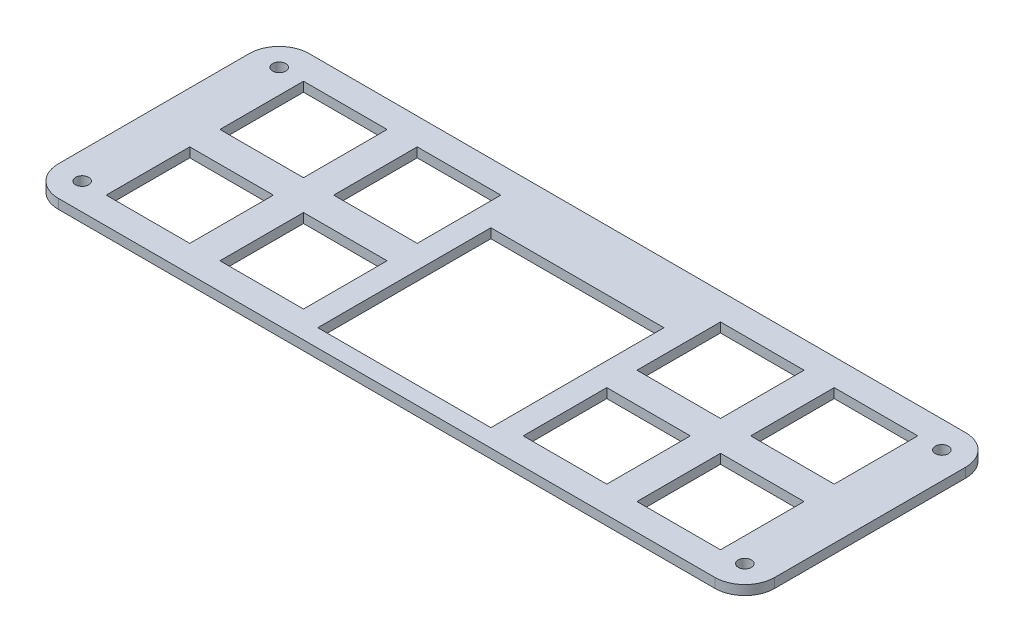
SolidWorks part; units mm, degrees
ref_plane "Ebene vorne" through (0, 0, 0) normal (0, 0, 1) x (1, 0, 0)
ref_plane "Ebene oben" through (0, 0, 0) normal (0, 1, 0) x (1, 0, 0)
ref_plane "Ebene rechts" through (0, 0, 0) normal (1, 0, 0) x (0, 0, -1)
sketch "Skizze1" plane through (0, 0, 0) normal (0, 1, 0) x (1, 0, 0)
  line L1 (-55, 21) -> (55, 21)
  line L2 (-60, 16) -> (-60, -16)
  line L3 (-55, -21) -> (55, -21)
  line L4 (60, 16) -> (60, -16)
  line L5 (-60, 21) -> (60, -21) construction
  line L6 (-60, -21) -> (60, 21) construction
  arc A0 (-60, -16) -> (-55, -21) centre (-55, -16) ccw
  arc A1 (55, -21) -> (60, -16) centre (55, -16) ccw
  arc A2 (55, 21) -> (60, 16) centre (55, 16) cw
  arc A3 (-55, 21) -> (-60, 16) centre (-55, 16) ccw
  point P0 (0, 0)
  dimension "D3" = 5
  dimension "D1" = 120
  dimension "D2" = 42
extrude "Aufsatz-Linear austragen1" add sketch "Skizze1" along normal blind 1.6
sketch "Skizze2" plane through (0, 1.6, 0) normal (0, 1, 0) x (1, 0, 0)
  line L0 (0, 13.4609) -> (0, -29.3692) construction
  line L1 (-51.45, 16.525) -> (-37.45, 16.525)
  line L2 (-51.45, 16.525) -> (-51.45, 2.525)
  line L3 (-51.45, 2.525) -> (-37.45, 2.525)
  line L4 (-37.45, 16.525) -> (-37.45, 2.525)
  line L5 (-51.45, -2.525) -> (-37.45, -2.525)
  line L6 (-51.45, -2.525) -> (-51.45, -16.525)
  line L7 (-51.45, -16.525) -> (-37.45, -16.525)
  line L8 (-37.45, -2.525) -> (-37.45, -16.525)
  line L9 (-32.4, 16.525) -> (-18.4, 16.525)
  line L10 (-32.4, 16.525) -> (-32.4, 2.525)
  line L11 (-32.4, 2.525) -> (-18.4, 2.525)
  line L12 (-18.4, 16.525) -> (-18.4, 2.525)
  line L13 (-32.4, -2.525) -> (-18.4, -2.525)
  line L14 (-32.4, -2.525) -> (-32.4, -16.525)
  line L15 (-32.4, -16.525) -> (-18.4, -16.525)
  line L16 (-18.4, -2.525) -> (-18.4, -16.525)
  line L17 (18.4, 16.525) -> (32.4, 16.525)
  line L18 (18.4, 16.525) -> (18.4, 2.525)
  line L19 (18.4, 2.525) -> (32.4, 2.525)
  line L20 (32.4, 16.525) -> (32.4, 2.525)
  line L21 (18.4, -2.525) -> (32.4, -2.525)
  line L22 (18.4, -2.525) -> (18.4, -16.525)
  line L23 (18.4, -16.525) -> (32.4, -16.525)
  line L24 (32.4, -2.525) -> (32.4, -16.525)
  line L25 (37.45, 16.525) -> (51.45, 16.525)
  line L26 (37.45, 16.525) -> (37.45, 2.525)
  line L27 (37.45, 2.525) -> (51.45, 2.525)
  line L28 (51.45, 16.525) -> (51.45, 2.525)
  line L29 (37.45, -2.525) -> (51.45, -2.525)
  line L30 (37.45, -2.525) -> (37.45, -16.525)
  line L31 (37.45, -16.525) -> (51.45, -16.525)
  line L32 (51.45, -2.525) -> (51.45, -16.525)
  line L33 (-13.0238, 0) -> (8.2164, 0) construction
  point P32 (-51.45, 9.525)
  point P33 (-51.45, -9.525)
  point P34 (-44.45, -16.525)
  point P35 (-25.4, -16.525)
  point P36 (25.4, -16.525)
  point P37 (44.45, -16.525)
  dimension "D1" = 14
  dimension "D2" = 19.05
  dimension "D3" = 19.05
  dimension "D4" = 19.05
  dimension "D5" = 50.8
extrude "Schnitt-Linear austragen1" cut sketch "Skizze2" against normal through all
sketch "Skizze3" plane through (0, 1.6, 0) normal (0, 1, 0) x (1, 0, 0)
  line L0 (0, -2.8845) -> (0, 15.8209) construction
  line L1 (-14.5, 10.96) -> (14.5, 10.96)
  line L2 (-14.5, 10.96) -> (-14.5, -18.04)
  line L3 (-14.5, -18.04) -> (14.5, -18.04)
  line L4 (14.5, 10.96) -> (14.5, -18.04)
  line L5 (-14.5, 10.96) -> (14.5, -18.04) construction
  line L6 (-14.5, -18.04) -> (14.5, 10.96) construction
  line L8 (-55, -21) -> (55, -21) construction
  point P0 (0, -3.54)
  dimension "D1" = 29
  dimension "D2" = 2.96
extrude "Schnitt-Linear austragen2" cut sketch "Skizze3" against normal through all
sketch "Skizze4" plane through (0, 1.6, 0) normal (0, 1, 0) x (1, 0, 0)
  line L0 (-60, 16) -> (-60, -16) construction
  line L1 (55, 21) -> (-55, 21) construction
  line L2 (-55, -21) -> (55, -21) construction
  line L3 (60, -16) -> (60, 16) construction
  circle A0 centre (-55.5, 16.5) radius 1.1
  circle A1 centre (-55.5, -16.5) radius 1.1
  circle A2 centre (55.5, 16.5) radius 1.1
  circle A3 centre (55.5, -16.5) radius 1.1
  dimension "D1" = 2.2
  dimension "D2" = 4.5
  dimension "D3" = 4.5
  dimension "D4" = 4.5
  dimension "D5" = 4.5
extrude "Schnitt-Linear austragen3" cut sketch "Skizze4" against normal through all
